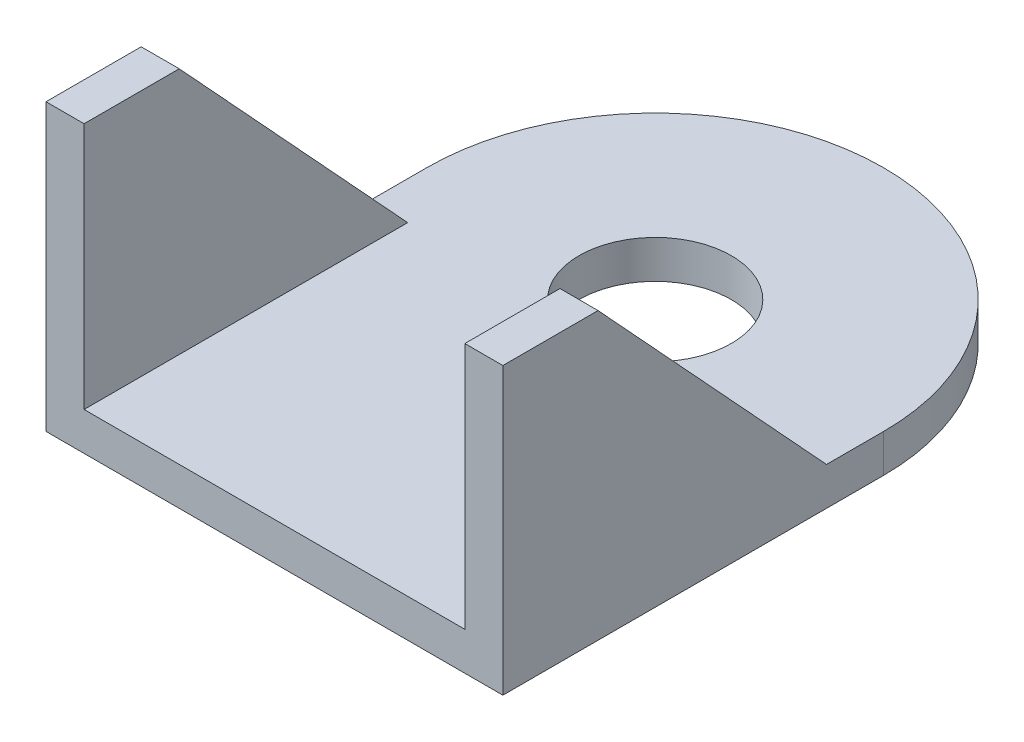
SolidWorks part; units mm, degrees
material "AISI 304"
ref_plane "前视基准面" through (0, 0, 0) normal (0, 0, 1) x (1, 0, 0)
ref_plane "上视基准面" through (0, 0, 0) normal (0, 1, 0) x (1, 0, 0)
ref_plane "右视基准面" through (0, 0, 0) normal (1, 0, 0) x (0, 0, -1)
sketch "草图1" plane through (0, 0, 0) normal (0, 1, 0) x (1, 0, 0)
  line L0 (-12, 0) -> (-12, -20)
  line L1 (-12, -20) -> (12, -20)
  line L2 (12, -20) -> (12, 0)
  circle A0 centre (0, 0) radius 4
  circle A1 centre (0, 0) radius 12
  dimension "D1" = 8
  dimension "D2" = 24
  dimension "D3" = 20
extrude "凸台-拉伸1" add sketch "草图1" along normal blind 2 contours A1 A0 | A1 L0 L1 L2 region at (0, 0, 14.3732) region at (0, 0, -11.6606)
sketch "草图3" plane through (12, 0, 0) normal (1, 0, 0) x (0, 0, -1)
  line L0 (-20, 2) -> (-20, 15)
  line L1 (-20, 15) -> (-15, 15)
  line L2 (-15, 15) -> (-3, 2)
  line L4 (-20, 2) -> (0, 2) construction
  line L5 (-3, 2) -> (-20, 2)
  dimension "D1" = 5
  dimension "D2" = 17
  dimension "D4" = 13
extrude "凸台-拉伸2" add sketch "草图3" against normal blind 2
ref_plane "基准面1" through (0, 0, 0) normal (0, 0, 1) x (1, 0, 0)
sketch "草图4" [suppressed] plane through (0, 0, 0) normal (0, 0, 1) x (1, 0, 0)
  circle A0 centre (0, 0) radius 41.9162
sketch "草图7" plane through (0, 0, 0) normal (0, -1, 0) x (1, 0, 0)
  circle A0 centre (0, 0) radius 9
split line "分割线1"
sketch "草图8" plane through (0, 0, 0) normal (0, -1, 0) x (1, 0, 0)
  circle A0 centre (0, 0) radius 12
split line "分割线2"
extrude "Boss-Extrude1" add sketch "草图3<2>" along normal blind 2 from surface starting at face at (-12, 1, 10)
sketch "草图3<2>" plane through (12, 0, 0) normal (1, 0, 0) x (0, 0, -1) same geometry as "草图3"
